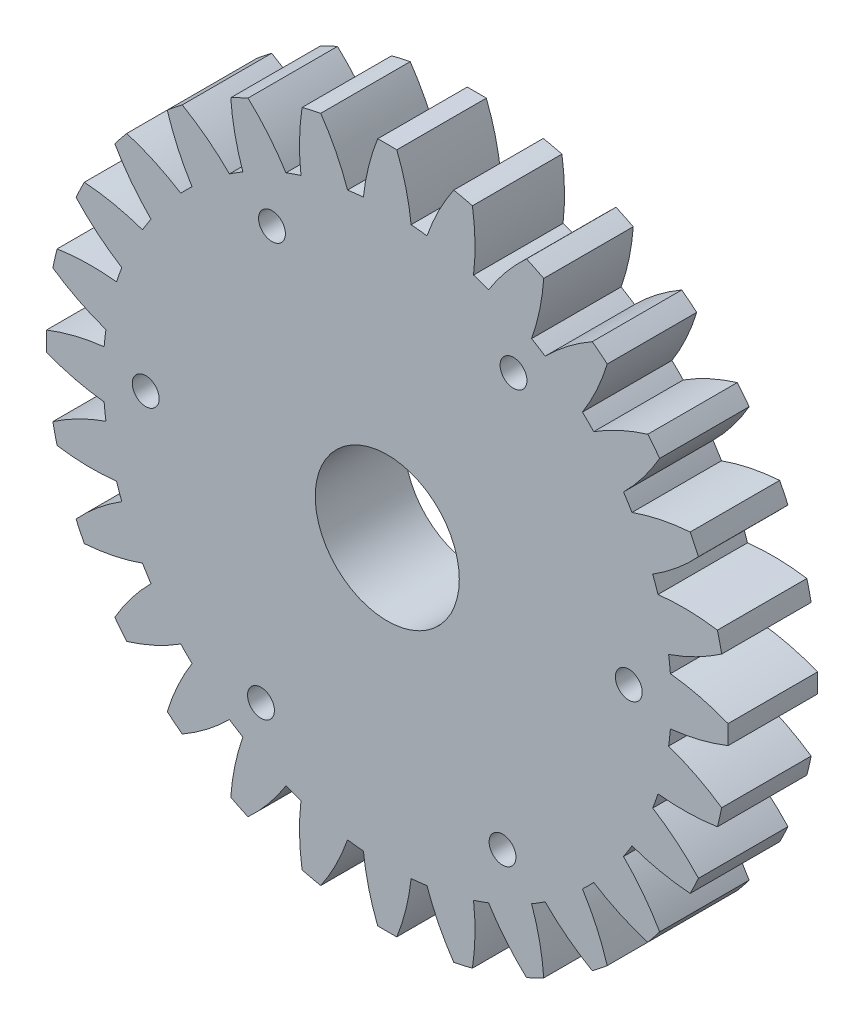
SolidWorks part; units mm, degrees
ref_plane "Front Plane" through (0, 0, 0) normal (0, 0, 1) x (1, 0, 0)
ref_plane "Top Plane" through (0, 0, 0) normal (0, 1, 0) x (1, 0, 0)
ref_plane "Right Plane" through (0, 0, 0) normal (1, 0, 0) x (0, 0, -1)
ref_plane "Plane1" through (0, 0, 5) normal (0, 0, 1) x (1, 0, 0)
sketch "Sketch1" plane through (0, 0, 5) normal (0, 0, 1) x (1, 0, 0)
  line L3 (0, 0) -> (-1.7774, 15.7752) construction
  arc A0 (-4.8209, 15.1253) -> (-5.6614, 14.8312) centre (0, 0) ccw
  arc A1 (-5.6614, 14.8312) -> (-7.7809, 17.3885) centre (-16.2618, 8.2026) ccw
  arc A2 (-7.7809, 17.3885) -> (-8.7436, 16.9249) centre (0, 0) ccw
  arc A3 (-8.7436, 16.9249) -> (-8.0657, 13.6733) centre (3.7261, 17.8282) ccw
  arc A4 (-8.0657, 13.6733) -> (-8.8197, 13.1996) centre (0, 0) ccw
  arc A5 (-8.8197, 13.1996) -> (-11.4551, 15.2211) centre (-17.6794, 4.3783) ccw
  arc A6 (-11.4551, 15.2211) -> (-12.2905, 14.5549) centre (0, 0) ccw
  arc A7 (-12.2905, 14.5549) -> (-10.9061, 11.5357) centre (-0.3345, 18.2104) ccw
  arc A8 (-10.9061, 11.5357) -> (-11.5357, 10.9061) centre (0, 0) ccw
  arc A9 (-11.5357, 10.9061) -> (-14.5549, 12.2905) centre (-18.2104, 0.3345) ccw
  arc A10 (-14.5549, 12.2905) -> (-15.2211, 11.4551) centre (0, 0) ccw
  arc A11 (-15.2211, 11.4551) -> (-13.1996, 8.8197) centre (-4.3783, 17.6794) ccw
  arc A12 (-13.1996, 8.8197) -> (-13.6733, 8.0657) centre (0, 0) ccw
  arc A13 (-13.6733, 8.0657) -> (-16.9249, 8.7436) centre (-17.8282, -3.7261) ccw
  arc A14 (-16.9249, 8.7436) -> (-17.3885, 7.7809) centre (0, 0) ccw
  arc A15 (-17.3885, 7.7809) -> (-14.8312, 5.6614) centre (-8.2026, 16.2618) ccw
  arc A16 (-14.8312, 5.6614) -> (-15.1253, 4.8209) centre (0, 0) ccw
  arc A17 (-15.1253, 4.8209) -> (-18.4462, 4.7582) centre (-16.5521, -7.5998) ccw
  arc A18 (-18.4462, 4.7582) -> (-18.684, 3.7165) centre (0, 0) ccw
  arc A19 (-18.684, 3.7165) -> (-15.7191, 2.2192) centre (-11.6155, 14.0289) ccw
  arc A20 (-15.7191, 2.2192) -> (-15.8188, 1.3343) centre (0, 0) ccw
  arc A21 (-15.8188, 1.3343) -> (-19.0425, 0.5343) centre (-14.446, -11.0924) ccw
  arc A22 (-19.0425, 0.5343) -> (-19.0425, -0.5343) centre (0, 0) ccw
  arc A23 (-19.0425, -0.5343) -> (-15.8188, -1.3343) centre (-14.446, 11.0924) ccw
  arc A24 (-15.8188, -1.3343) -> (-15.7191, -2.2192) centre (0, 0) ccw
  arc A25 (-15.7191, -2.2192) -> (-18.684, -3.7165) centre (-11.6155, -14.0289) ccw
  arc A26 (-18.684, -3.7165) -> (-18.4462, -4.7582) centre (0, 0) ccw
  arc A27 (-18.4462, -4.7582) -> (-15.1253, -4.8209) centre (-16.5521, 7.5998) ccw
  arc A28 (-15.1253, -4.8209) -> (-14.8312, -5.6614) centre (0, 0) ccw
  arc A29 (-14.8312, -5.6614) -> (-17.3885, -7.7809) centre (-8.2026, -16.2618) ccw
  arc A30 (-17.3885, -7.7809) -> (-16.9249, -8.7436) centre (0, 0) ccw
  arc A31 (-16.9249, -8.7436) -> (-13.6733, -8.0657) centre (-17.8282, 3.7261) ccw
  arc A32 (-13.6733, -8.0657) -> (-13.1996, -8.8197) centre (0, 0) ccw
  arc A33 (-13.1996, -8.8197) -> (-15.2211, -11.4551) centre (-4.3783, -17.6794) ccw
  arc A34 (-15.2211, -11.4551) -> (-14.5549, -12.2905) centre (0, 0) ccw
  arc A35 (-14.5549, -12.2905) -> (-11.5357, -10.9061) centre (-18.2104, -0.3345) ccw
  arc A36 (-11.5357, -10.9061) -> (-10.9061, -11.5357) centre (0, 0) ccw
  arc A37 (-10.9061, -11.5357) -> (-12.2905, -14.5549) centre (-0.3345, -18.2104) ccw
  arc A38 (-12.2905, -14.5549) -> (-11.4551, -15.2211) centre (0, 0) ccw
  arc A39 (-11.4551, -15.2211) -> (-8.8197, -13.1996) centre (-17.6794, -4.3783) ccw
  arc A40 (-8.8197, -13.1996) -> (-8.0657, -13.6733) centre (0, 0) ccw
  arc A41 (-8.0657, -13.6733) -> (-8.7436, -16.9249) centre (3.7261, -17.8282) ccw
  arc A42 (-8.7436, -16.9249) -> (-7.7809, -17.3885) centre (0, 0) ccw
  arc A43 (-7.7809, -17.3885) -> (-5.6614, -14.8312) centre (-16.2618, -8.2026) ccw
  arc A44 (-5.6614, -14.8312) -> (-4.8209, -15.1253) centre (0, 0) ccw
  arc A45 (-4.8209, -15.1253) -> (-4.7582, -18.4462) centre (7.5998, -16.5521) ccw
  arc A46 (-4.7582, -18.4462) -> (-3.7165, -18.684) centre (0, 0) ccw
  arc A47 (-3.7165, -18.684) -> (-2.2192, -15.7191) centre (-14.0289, -11.6155) ccw
  arc A48 (-2.2192, -15.7191) -> (-1.3343, -15.8188) centre (0, 0) ccw
  arc A49 (-1.3343, -15.8188) -> (-0.5343, -19.0425) centre (11.0924, -14.446) ccw
  arc A50 (-0.5343, -19.0425) -> (0.5343, -19.0425) centre (0, 0) ccw
  arc A51 (0.5343, -19.0425) -> (1.3343, -15.8188) centre (-11.0924, -14.446) ccw
  arc A52 (1.3343, -15.8188) -> (2.2192, -15.7191) centre (0, 0) ccw
  arc A53 (2.2192, -15.7191) -> (3.7165, -18.684) centre (14.0289, -11.6155) ccw
  arc A54 (3.7165, -18.684) -> (4.7582, -18.4462) centre (0, 0) ccw
  arc A55 (4.7582, -18.4462) -> (4.8209, -15.1253) centre (-7.5998, -16.5521) ccw
  arc A56 (4.8209, -15.1253) -> (5.6614, -14.8312) centre (0, 0) ccw
  arc A57 (5.6614, -14.8312) -> (7.7809, -17.3885) centre (16.2618, -8.2026) ccw
  arc A58 (7.7809, -17.3885) -> (8.7436, -16.9249) centre (0, 0) ccw
  arc A59 (8.7436, -16.9249) -> (8.0657, -13.6733) centre (-3.7261, -17.8282) ccw
  arc A60 (8.0657, -13.6733) -> (8.8197, -13.1996) centre (0, 0) ccw
  arc A61 (8.8197, -13.1996) -> (11.4551, -15.2211) centre (17.6794, -4.3783) ccw
  arc A62 (11.4551, -15.2211) -> (12.2905, -14.5549) centre (0, 0) ccw
  arc A63 (12.2905, -14.5549) -> (10.9061, -11.5357) centre (0.3345, -18.2104) ccw
  arc A64 (10.9061, -11.5357) -> (11.5357, -10.9061) centre (0, 0) ccw
  arc A65 (11.5357, -10.9061) -> (14.5549, -12.2905) centre (18.2104, -0.3345) ccw
  arc A66 (14.5549, -12.2905) -> (15.2211, -11.4551) centre (0, 0) ccw
  arc A67 (15.2211, -11.4551) -> (13.1996, -8.8197) centre (4.3783, -17.6794) ccw
  arc A68 (13.1996, -8.8197) -> (13.6733, -8.0657) centre (0, 0) ccw
  arc A69 (13.6733, -8.0657) -> (16.9249, -8.7436) centre (17.8282, 3.7261) ccw
  arc A70 (16.9249, -8.7436) -> (17.3885, -7.7809) centre (0, 0) ccw
  arc A71 (17.3885, -7.7809) -> (14.8312, -5.6614) centre (8.2026, -16.2618) ccw
  arc A72 (14.8312, -5.6614) -> (15.1253, -4.8209) centre (0, 0) ccw
  arc A73 (15.1253, -4.8209) -> (18.4462, -4.7582) centre (16.5521, 7.5998) ccw
  arc A74 (18.4462, -4.7582) -> (18.684, -3.7165) centre (0, 0) ccw
  arc A75 (18.684, -3.7165) -> (15.7191, -2.2192) centre (11.6155, -14.0289) ccw
  arc A76 (15.7191, -2.2192) -> (15.8188, -1.3343) centre (0, 0) ccw
  arc A77 (15.8188, -1.3343) -> (19.0425, -0.5343) centre (14.446, 11.0924) ccw
  arc A78 (19.0425, -0.5343) -> (19.0425, 0.5343) centre (0, 0) ccw
  arc A79 (19.0425, 0.5343) -> (15.8188, 1.3343) centre (14.446, -11.0924) ccw
  arc A80 (15.8188, 1.3343) -> (15.7191, 2.2192) centre (0, 0) ccw
  arc A81 (15.7191, 2.2192) -> (18.684, 3.7165) centre (11.6155, 14.0289) ccw
  arc A82 (18.684, 3.7165) -> (18.4462, 4.7582) centre (0, 0) ccw
  arc A83 (18.4462, 4.7582) -> (15.1253, 4.8209) centre (16.5521, -7.5998) ccw
  arc A84 (15.1253, 4.8209) -> (14.8312, 5.6614) centre (0, 0) ccw
  arc A85 (14.8312, 5.6614) -> (17.3885, 7.7809) centre (8.2026, 16.2618) ccw
  arc A86 (17.3885, 7.7809) -> (16.9249, 8.7436) centre (0, 0) ccw
  arc A87 (16.9249, 8.7436) -> (13.6733, 8.0657) centre (17.8282, -3.7261) ccw
  arc A88 (13.6733, 8.0657) -> (13.1996, 8.8197) centre (0, 0) ccw
  arc A89 (13.1996, 8.8197) -> (15.2211, 11.4551) centre (4.3783, 17.6794) ccw
  arc A90 (15.2211, 11.4551) -> (14.5549, 12.2905) centre (0, 0) ccw
  arc A91 (14.5549, 12.2905) -> (11.5357, 10.9061) centre (18.2104, 0.3345) ccw
  arc A92 (11.5357, 10.9061) -> (10.9061, 11.5357) centre (0, 0) ccw
  arc A93 (10.9061, 11.5357) -> (12.2905, 14.5549) centre (0.3345, 18.2104) ccw
  arc A94 (12.2905, 14.5549) -> (11.4551, 15.2211) centre (0, 0) ccw
  arc A95 (11.4551, 15.2211) -> (8.8197, 13.1996) centre (17.6794, 4.3783) ccw
  arc A96 (8.8197, 13.1996) -> (8.0657, 13.6733) centre (0, 0) ccw
  arc A97 (8.0657, 13.6733) -> (8.7436, 16.9249) centre (-3.7261, 17.8282) ccw
  arc A98 (8.7436, 16.9249) -> (7.7809, 17.3885) centre (0, 0) ccw
  arc A99 (7.7809, 17.3885) -> (5.6614, 14.8312) centre (16.2618, 8.2026) ccw
  arc A100 (5.6614, 14.8312) -> (4.8209, 15.1253) centre (0, 0) ccw
  arc A101 (4.8209, 15.1253) -> (4.7582, 18.4462) centre (-7.5998, 16.5521) ccw
  arc A102 (4.7582, 18.4462) -> (3.7165, 18.684) centre (0, 0) ccw
  arc A103 (3.7165, 18.684) -> (2.2192, 15.7191) centre (14.0289, 11.6155) ccw
  arc A104 (2.2192, 15.7191) -> (1.3343, 15.8188) centre (0, 0) ccw
  arc A105 (1.3343, 15.8188) -> (0.5343, 19.0425) centre (-11.0924, 14.446) ccw
  arc A106 (0.5343, 19.0425) -> (-0.5343, 19.0425) centre (0, 0) ccw
  arc A107 (-0.5343, 19.0425) -> (-1.3343, 15.8188) centre (11.0924, 14.446) ccw
  arc A108 (-1.3343, 15.8188) -> (-2.2192, 15.7191) centre (0, 0) ccw
  arc A109 (-2.2192, 15.7191) -> (-3.7165, 18.684) centre (-14.0289, 11.6155) ccw
  arc A110 (-3.7165, 18.684) -> (-4.7582, 18.4462) centre (0, 0) ccw
  arc A111 (-4.7582, 18.4462) -> (-4.8209, 15.1253) centre (7.5998, 16.5521) ccw
  circle A112 centre (0, 0) radius 4.025
  circle A113 centre (-6.4405, 11.8647) radius 0.75
  circle A114 centre (7.0548, 11.51) radius 0.75
  circle A115 centre (13.4953, -0.3547) radius 0.75
  circle A116 centre (6.4405, -11.8647) radius 0.75
  circle A117 centre (-7.0548, -11.51) radius 0.75
  circle A118 centre (-13.4953, 0.3547) radius 0.75
  point P186 (0, 0)
  dimension "D2" = 8.05
  dimension "D1" = 19.05
  dimension "D3" = 1.5
  dimension "D4" = 13.5
  dimension "D5" = 6
extrude "Boss-Extrude1" add sketch "Sketch1" against normal blind 5
